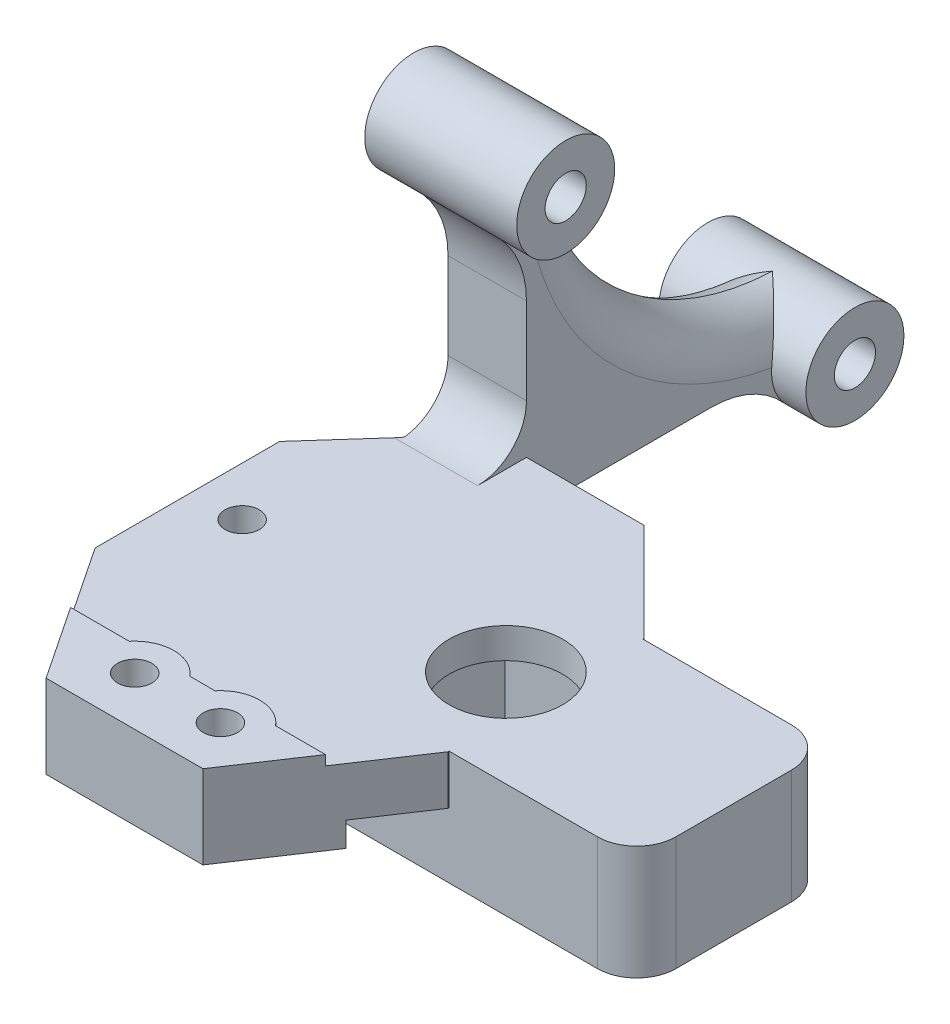
SolidWorks part; units mm, degrees
ref_plane "Front Plane" through (0, 0, 0) normal (0, 0, 1) x (1, 0, 0)
ref_plane "Top Plane" through (0, 0, 0) normal (0, 1, 0) x (1, 0, 0)
ref_plane "Right Plane" through (0, 0, 0) normal (1, 0, 0) x (0, 0, -1)
sketch "Sketch2" plane through (0, 0, 0) normal (0, 1, 0) x (1, 0, 0)
  line L0 (0, 33.8197) -> (10, 45)
  line L1 (0, 0) -> (60, 0)
  line L2 (0, 0) -> (0, 45)
  line L3 (0, 45) -> (60, 45)
  line L4 (60, 0) -> (60, 45)
  line L5 (0, 15) -> (10, 0)
  line L6 (60, 15) -> (36, 15)
  line L7 (36, 15) -> (26, 0)
  line L8 (26, 45) -> (36, 35)
  line L9 (36, 35) -> (60, 35)
  line L10 (0, 25) -> (60, 25) construction
  line L11 (37.3, 30.4) -> (37.3, 19.6)
  line L12 (44.5, 30.4) -> (26.5, 30.4)
  line L13 (44.5, 30.4) -> (44.5, 19.6)
  line L14 (44.5, 19.6) -> (26.5, 19.6)
  line L15 (26.5, 30.4) -> (26.5, 19.6)
  line L16 (44.5, 30.4) -> (26.5, 19.6) construction
  line L17 (44.5, 19.6) -> (26.5, 30.4) construction
  circle A0 centre (5, 25) radius 1.75
  circle A1 centre (13, 5) radius 1.75
  circle A2 centre (23, 5) radius 1.75
  point P17 (35.5, 25)
  dimension "D13" = 3.5
  dimension "D1" = 45
  dimension "D2" = 60
  dimension "D3" = 15
  dimension "D4" = 10
  dimension "D5" = 15
  dimension "D6" = 10
  dimension "D7" = 16
  dimension "D8" = 10
  dimension "D9" = 16
  dimension "D10" = 10
  dimension "D11" = 20
  dimension "D12" = 10
  dimension "D14" = 10
  dimension "D15" = 5
  dimension "D16" = 3
  dimension "D17" = 5
  dimension "D18" = 10
  dimension "D19" = 18
  dimension "D20" = 4.6
  dimension "D21" = 15.5
  dimension "D22" = 10.8
extrude "Boss-Extrude1" add sketch "Sketch2" along normal blind 5 contours L9 L8 L3 L0 L2 L5 L1 L7 L6 L4 A2 A1 A0 L15 L12 L13 L14 | L14 L13 L12 L11 region at (24.916, 0, -23.5142) region at (40.9, 0, -25)
fillet "Fillet1" 2 edges at (37.3, 2.5, -19.6) (37.3, 2.5, -30.4) type full round first side face at (31.9, 2.5, -19.6) second side face at (31.9, 2.5, -30.4) middle face at (37.3, 2.5, -25)
fillet "Fillet2" 2 edges at (26.5, 2.5, -19.6) (26.5, 2.5, -30.4) type full round first side face at (29.2, 2.5, -19.6) second side face at (29.2, 2.5, -30.4) middle face at (26.5, 2.5, -25)
fillet "Fillet3" 2 edges at (60, 2.5, -35) (60, 2.5, -15) type full round first side face at (48, 2.5, -35) second side face at (48, 2.5, -15) middle face at (60, 2.5, -25)
sketch "Sketch3" plane through (0, 0, 0) normal (0, -1, 0) x (1, 0, 0)
  line L5 (14.4, -15.1087) -> (49.4, -15.1087)
  line L6 (14.4, -15.1087) -> (14.4, -34.8913)
  line L11 (14.4, -34.8913) -> (49.4, -34.8913)
  line L12 (49.4, -15.1087) -> (49.4, -34.8913)
  line L13 (14.4, -15.1087) -> (49.4, -34.8913) construction
  line L14 (14.4, -34.8913) -> (49.4, -15.1087) construction
  line L15 (43.4, -18.5) -> (20.4, -18.5)
  line L16 (43.4, -18.5) -> (43.4, -31.5)
  line L17 (43.4, -31.5) -> (20.4, -31.5)
  line L18 (20.4, -18.5) -> (20.4, -31.5)
  line L19 (43.4, -18.5) -> (20.4, -31.5) construction
  line L20 (43.4, -31.5) -> (20.4, -18.5) construction
  circle A1 centre (31.9, -25) radius 6.5
  point P0 (31.9, -25)
  point P5 (31.9, -25)
  line M12 (36, -35) -> (50, -35)
  line M14 (50, -15) -> (36, -15)
  line M15 (36, -15) -> (26, 0)
  line M21 (26, -45) -> (36, -35)
  arc M27 (50, -35) -> (50, -15) centre (50, -25) ccw
  dimension "D1" = 6
  dimension "D3" = 13
  dimension "D2" = 23
  dimension "D4" = 13
extrude "Boss-Extrude2" add sketch "Sketch3" along normal blind 5.5 contours L12 L5 L6 L11 L18 L15 L16 L17 M27 M14 M15 M21 M12 region at (31.9, 0, -15.5107)
sketch "Sketch4" plane through (0, 0, 0) normal (0, -1, 0) x (1, 0, 0)
  line L4 (43.4, -18.5) -> (20.4, -18.5)
  line L5 (20.4, -18.5) -> (20.4, -31.5)
  line L6 (20.4, -31.5) -> (43.4, -31.5)
  line L7 (43.4, -31.5) -> (43.4, -18.5)
  line L8 (43.4, -18.5) -> (20.4, -18.5)
  line L9 (20.4, -18.5) -> (20.4, -31.5)
  line L10 (20.4, -31.5) -> (43.4, -31.5)
  line L11 (43.4, -31.5) -> (43.4, -18.5)
  dimension "D1" = 0
extrude "Cut-Extrude1" cut sketch "Sketch4" against normal blind 3.5
sketch "Sketch6" plane through (0, 0, 0) normal (0, -1, 0) x (1, 0, 0)
  line L0 (50, -15) -> (49.4, -15)
  line L1 (50, -35) -> (49.4, -35)
  line L2 (36, -35) -> (50, -35) construction
  line L9 (49.4, -15.1087) -> (49.4, -34.8913) construction
  line L10 (50, -15) -> (36, -15) construction
  line L12 (49.4, -15) -> (49.4, -35)
  arc A0 (50, -35) -> (50, -15) centre (50, -25) ccw construction
  arc A1 (50, -35) -> (50, -15) centre (50, -25) ccw
extrude "Cut-Extrude2" cut sketch "Sketch6" against normal through all both and the other way through all contours L0 L12 L1 A1 body kept at (26, 0, 0)
sketch "Sketch8" plane through (0, 0, 0) normal (0, -1, 0) x (1, 0, 0)
  line L0 (49.4, -35) -> (49.4, -34.8913) construction
  line L1 (14.4, -34.8913) -> (49.4, -34.8913) construction
  line L2 (36, -35) -> (49.4, -35) construction
  line L3 (49.4, -15.1087) -> (49.4, -15) construction
  line L4 (14.4, -15.1087) -> (49.4, -15.1087) construction
  line L5 (49.4, -15) -> (36, -15) construction
  line L6 (49.4, -35) -> (49.4, -34.8913)
  line L7 (36, -34.8913) -> (49.4, -34.8913)
  line L8 (36, -35) -> (49.4, -35)
  line L9 (49.4, -15.1087) -> (49.4, -15)
  line L10 (36, -15.1087) -> (49.4, -15.1087)
  line L11 (49.4, -15) -> (36, -15)
  line L12 (36, -35) -> (36, -34.8913)
  line L13 (36, -15) -> (36, -15.1087)
extrude "Cut-Extrude3" cut sketch "Sketch8" against normal through all both and the other way through all
fillet "Fillet4" radius 4 2 edges at (49.4, -0.25, -15.1087) (49.4, -0.25, -34.8913)
sketch "Sketch10" plane through (0, 0, -45) normal (0, 0, -1) x (-1, 0, 0)
  line L1 (-14, 0) -> (-6, 0)
  line L2 (-14, 0) -> (-14, 30)
  line L3 (-14, 30) -> (-6, 30)
  line L4 (-6, 0) -> (-6, 30)
  line L5 (-10, 5) -> (-10, 0) construction
  point P6 (-10, 0)
  dimension "D3" = 4
extrude "Boss-Extrude10" add sketch "Sketch10" along normal blind 30
sketch "Sketch24" plane through (14, 0, 0) normal (1, 0, 0) x (0, 0, -1)
  circle A0 centre (45, 30) radius 5
  circle A1 centre (75, 0) radius 5
  line M5 (45, 0) -> (75, 0)
  line M6 (75, 0) -> (75, 30)
extrude "Boss-Extrude11" add sketch "Sketch24" along normal blind 3.5 and the other way blind 11.5 contours A1 M5 M6 | A1 M6 M5 | A0 region at (14, -0.7074, -75.7074) region at (14, 2.1221, -72.8779)
ref_axis "Axis1" through (-1.7812, 0, -75) along (1, 0, 0)
ref_axis "Axis2" through (-6.8947, 30, -45) along (1, 0, 0)
sketch "Sketch25" plane through (14, 0, 0) normal (1, 0, 0) x (0, 0, -1)
  line L0 (50, 30) -> (75, 30)
  line L1 (75, 30) -> (75, 5)
  arc A0 (50, 30) -> (75, 5) centre (75, 30) ccw
  circle A2 centre (45, 30) radius 5 construction
extrude "Cut-Extrude9" cut sketch "Sketch25" against normal up to next
fillet "Fillet13" radius 10 2 edges at (10, 0, -70) (10, 25, -45)
sketch "Sketch26" plane through (0, 0, 0) normal (0, -1, 0) x (1, 0, 0)
  line L0 (6, -45) -> (6, -40.5279)
  line L1 (0, -33.8197) -> (10, -45) construction
  line L2 (6, -40.5279) -> (10, -45)
  line L3 (6, -45) -> (10, -45)
extrude "Boss-Extrude12" add sketch "Sketch26" against normal up to surface (5 mm away) up to face at (28.0838, 5, -25.588)
fillet "Fillet14" radius 5 1 edges at (10, 5, -45)
fillet "Fillet15" radius 5 2 edges at (14, 12.3223, -57.3223) (6, 12.3223, -57.3223)
sketch "Sketch12" plane through (0, -5.5, 0) normal (0, -1, 0) x (1, 0, 0)
  line L0 (43.4, -25) -> (20.4, -25) construction
  line L1 (43.4, -18.5) -> (43.4, -31.5) construction
  line L2 (20.4, -18.5) -> (20.4, -31.5) construction
  circle A0 centre (18.1, -25) radius 1
  circle A1 centre (45.7, -25) radius 1
  dimension "D1" = 2
  dimension "D2" = 2.3
  dimension "D3" = 27.6
extrude "Cut-Extrude5" cut sketch "Sketch12" against normal blind 32
sketch "Sketch21" plane through (0, -5.5, 0) normal (0, -1, 0) x (1, 0, 0)
  line L0 (20.4, -18.5) -> (20.4, -31.5) construction
  line L1 (20.4, -18.5) -> (20.4, -31.5)
  line L2 (20.4, -18.5) -> (25.6108, -18.5)
  line L3 (43.4, -18.5) -> (20.4, -18.5) construction
  line L4 (25.6108, -18.5) -> (25.6108, -31.5)
  line L5 (43.4, -31.5) -> (20.4, -31.5) construction
  line L6 (25.6108, -31.5) -> (20.4, -31.5)
  line L7 (49.4, -19.1087) -> (49.4, -30.8913)
  line L8 (45.4, -34.8913) -> (55.1343, -34.8913)
  line L9 (55.1343, -34.8913) -> (55.1343, -15.1087)
  line L10 (55.1343, -15.1087) -> (45.4, -15.1087)
  arc A0 (22.3648, -25.55) -> (22.3648, -24.45) centre (23.2, -25) ccw construction
  circle A1 centre (23.2, -25) radius 1
  circle A2 centre (18.1, -25) radius 1 construction
  circle A3 centre (18.1, -25) radius 1
  arc A4 (51.6352, -24.45) -> (51.6352, -25.55) centre (50.8, -25) ccw construction
  circle A5 centre (50.8, -25) radius 1
  arc A6 (45.4, -34.8913) -> (49.4, -30.8913) centre (45.4, -30.8913) ccw construction
  arc A7 (49.4, -19.1087) -> (45.4, -15.1087) centre (45.4, -19.1087) ccw construction
  arc A8 (49.4, -19.1087) -> (45.4, -15.1087) centre (45.4, -19.1087) ccw
  arc A9 (45.4, -34.8913) -> (49.4, -30.8913) centre (45.4, -30.8913) ccw
  circle M1 centre (18.1, -25) radius 1
extrude "Boss-Extrude6" add sketch "Sketch21" against normal up to surface (10.5 mm away) contours M1 region at (18.1, -5.5, -25) up to face at (18.1, 5, -24)
extrude "Boss-Extrude7" add sketch "Sketch21<3>" against normal up to surface (9 mm away) contours A1 region at (23.2, -5.5, -25) up to face at (31.9, 3.5, -25)
sketch "Sketch21<3>" plane through (0, -5.5, 0) normal (0, -1, 0) x (1, 0, 0) same geometry as "Sketch21"
extrude "Boss-Extrude8" add sketch "Sketch21<4>" against normal up to surface (10.5 mm away) contours L9 L10 A8 L7 A9 L8 up to face at (45.7, 5, -24)
sketch "Sketch21<4>" plane through (0, -5.5, 0) normal (0, -1, 0) x (1, 0, 0) same geometry as "Sketch21"
fillet "Fillet12" radius 4 2 edges at (55.1343, -0.25, -15.1087) (55.1343, -0.25, -34.8913)
sketch "Sketch27" plane through (0, -5.5, 0) normal (0, -1, 0) x (1, 0, 0)
  line L1 (20.4, -18.5) -> (43.4, -18.5)
  line L2 (20.4, -18.5) -> (20.4, -31.5)
  line L3 (20.4, -31.5) -> (43.4, -31.5)
  line L4 (43.4, -18.5) -> (43.4, -31.5)
  circle A0 centre (45.7, -25) radius 1
  circle A2 centre (23.2, -25) radius 1
  circle M12 centre (45.7, -25) radius 1
  line M13 (20.4, -31.5) -> (20.4, -18.5)
  line M14 (20.4, -18.5) -> (43.4, -18.5)
  line M15 (43.4, -18.5) -> (43.4, -31.5)
  line M16 (43.4, -31.5) -> (20.4, -31.5)
extrude "Cut-Extrude11" cut sketch "Sketch27" against normal blind 9 contours A2 region at (23.2, -5.5, -25)
extrude "Boss-Extrude13" add sketch "Sketch27<4>" against normal up to surface (10.5 mm away) contours A2 | A2 M13 M16 M15 M14 | M12 region at (31.9924, -5.5, -25) region at (45.7, -5.5, -25) region at (23.2, -5.5, -25) up to face at (45.7, 5, -24)
sketch "Sketch27<4>" plane through (0, -5.5, 0) normal (0, -1, 0) x (1, 0, 0) same geometry as "Sketch27"
sketch "Sketch28" plane through (0, 5, 0) normal (0, 1, 0) x (1, 0, 0)
  line L0 (5, 25) -> (31.9, 25)
  circle A0 centre (31.9, 25) radius 5.7981
extrude "Cut-Extrude12" cut sketch "Sketch28" against normal up to surface (10.5 mm away) contours A0 region at (31.9, 5, -19.3659) up to face at (40.499, -5.5, -25)
sketch "Sketch29" plane through (0, -5.5, 0) normal (0, -1, 0) x (1, 0, 0)
  line L0 (31.9, -25) -> (25.8, -25)
  line L1 (25.8, -19) -> (25.8, -31)
  line L2 (25.8, -31) -> (48.8, -31)
  line L3 (48.8, -31) -> (48.8, -19)
  line L4 (48.8, -19) -> (25.8, -19)
  point P6 (25.8, -25)
sketch "Sketch30" plane through (0, -5.5, 0) normal (0, -1, 0) x (1, 0, 0)
  line L1 (14.4, -15.1087) -> (51.1343, -15.1087)
  line L2 (14.4, -15.1087) -> (14.4, -34.8913)
  line L3 (14.4, -34.8913) -> (51.1343, -34.8913)
  line L4 (55.1343, -19.1087) -> (55.1343, -30.8913)
  arc A0 (51.1343, -34.8913) -> (55.1343, -30.8913) centre (51.1343, -30.8913) ccw
  arc A1 (55.1343, -19.1087) -> (51.1343, -15.1087) centre (51.1343, -19.1087) ccw
  circle A2 centre (31.9, -25) radius 5.7981
  circle M8 centre (31.9, -25) radius 5.7981
  line M9 (55.1343, -30.8913) -> (55.1343, -19.1087)
  arc M10 (55.1343, -19.1087) -> (51.1343, -15.1087) centre (51.1343, -19.1087) ccw
  line M11 (51.1343, -15.1087) -> (14.4, -15.1087)
  line M12 (14.4, -15.1087) -> (14.4, -34.8913)
  line M13 (14.4, -34.8913) -> (51.1343, -34.8913)
  arc M14 (51.1343, -34.8913) -> (55.1343, -30.8913) centre (51.1343, -30.8913) ccw
  dimension "D1" = 4
extrude "Boss-Extrude14" add sketch "Sketch30" along normal blind 1.15 contours M14 M9 M10 M11 M12 M13 M8 region at (32.7671, -5.5, -15.5615)
sketch "Sketch31" plane through (0, -6.65, 0) normal (0, -1, 0) x (1, 0, 0)
  line L1 (25.8, -19) -> (48.8, -19)
  line L2 (25.8, -19) -> (25.8, -31)
  line L3 (25.8, -31) -> (48.8, -31)
  line L4 (48.8, -19) -> (48.8, -31)
extrude "Cut-Extrude15" cut sketch "Sketch31" against normal blind 8.55
sketch "Sketch32" plane through (17.5, 0, 0) normal (1, 0, 0) x (0, 0, -1)
  circle A0 centre (45, 30) radius 5
extrude "Boss-Extrude15" add sketch "Sketch32" along normal blind 0.5
ref_axis "Axis3" through (31.9, -13.9128, -25) along (0, 1, 0)
ref_axis "Axis4" through (5, 17.3569, -25) along (0, -1, 0)
sketch "Sketch34" plane through (0, 5, 0) normal (0, 1, 0) x (1, 0, 0)
  line L0 (5, 25) -> (5, -15.6306)
  line L1 (31.9, 25) -> (31.9, -17.1203)
  line L2 (31.9, 25) -> (22.8222, 4.9602)
  line L3 (5, 25) -> (14.0778, 4.9602)
  line L4 (14.0778, 4.9602) -> (22.8222, 4.9602)
  dimension "D1" = 24.37
  dimension "D2" = 24.37
sketch "Sketch35" plane through (0, 5, 0) normal (0, 1, 0) x (1, 0, 0)
  circle A6 centre (13, 5) radius 2.6052
  circle A7 centre (23, 5) radius 2.0489
extrude "Boss-Extrude18" add sketch "Sketch35" against normal up to surface (5 mm away) up to face at (18.32, 0, -30.4658)
sketch "Sketch36" plane through (0, 5, 0) normal (0, 1, 0) x (1, 0, 0)
  circle A0 centre (14.0778, 4.9602) radius 1.75
  circle A1 centre (22.8222, 4.9602) radius 1.75
  dimension "D1" = 3.5
  dimension "D2" = 3.5
extrude "Cut-Extrude21" cut sketch "Sketch36" against normal blind 5 contours A0 | A1
ref_axis "Axis7" through (22.8222, -11.9125, -4.9602) along (0, 1, 0)
ref_axis "Axis8" through (14.0778, -14.1428, -4.9602) along (0, 1, 0)
sketch "Sketch37" plane through (0, 5, 0) normal (0, 1, 0) x (1, 0, 0)
  line L0 (10, 0) -> (26, 0)
  line L1 (26, 0) -> (31, 7.5)
  line L2 (36, 15) -> (26, 0) construction
  line L3 (31, 7.5) -> (5, 7.5)
  line L4 (0, 15) -> (10, 0) construction
  line L5 (5, 7.5) -> (10, 0)
  circle A0 centre (14.0778, 4.9602) radius 1.75
  circle A1 centre (22.8222, 4.9602) radius 1.75
  circle A2 centre (22.8222, 4.9602) radius 4
  circle A3 centre (14.0778, 4.9602) radius 4
  circle M1 centre (14.0778, 4.9602) radius 1.75
  circle M2 centre (22.8222, 4.9602) radius 1.75
  line M17 (0, 15) -> (10, 0)
  line M18 (10, 0) -> (26, 0)
  line M19 (26, 0) -> (36, 15)
extrude "Boss-Extrude20" add sketch "Sketch37" along normal blind 1 contours M1 | L3 A2 | A3 L3 A2 M17 M18 M19 | L3 A2 M2 | A3 region at (7.7252, 5, -3.9001) region at (26.4906, 5, -6.2743) region at (22.8222, 5, -8.0943) region at (14.0778, 5, -4.9602)
sketch "Sketch38" plane through (2.5, 0, 0) normal (-1, 0, 0) x (0, 0, 1)
  circle A0 centre (-45, 30) radius 2.1
  circle A1 centre (-75, 0) radius 2.1
extrude "Cut-Extrude22" cut sketch "Sketch38" against normal through all
sketch "Sketch39" plane through (0, 0, 0) normal (0, -1, 0) x (1, 0, 0)
  line L0 (10, 0) -> (26, 0)
  line L1 (26, 0) -> (31.8329, -8.7493)
  line L2 (36, -15) -> (26, 0) construction
  line L3 (31.8329, -8.7493) -> (4.1671, -8.7493)
  line L4 (0, -15) -> (10, 0) construction
  line L5 (4.1671, -8.7493) -> (10, 0)
  circle A0 centre (14.0778, -4.9602) radius 1.75
  circle A1 centre (22.8222, -4.9602) radius 1.75
extrude "Boss-Extrude21" add sketch "Sketch39" along normal blind 2.5
